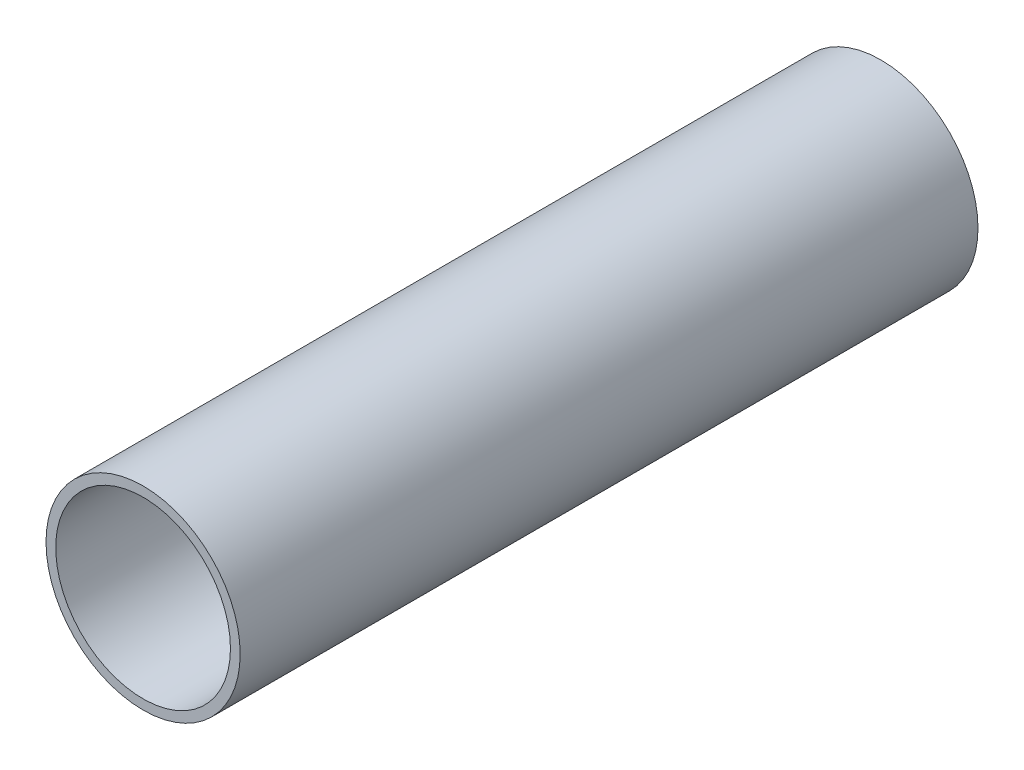
SolidWorks part; units mm, degrees
ref_plane "Front Plane" through (0, 0, 0) normal (0, 0, 1) x (1, 0, 0)
ref_plane "Top Plane" through (0, 0, 0) normal (0, 1, 0) x (1, 0, 0)
ref_plane "Right Plane" through (0, 0, 0) normal (1, 0, 0) x (0, 0, -1)
sketch "Sketch1" plane through (0, 0, 0) normal (0, 0, 1) x (1, 0, 0)
  circle A0 centre (35, 0) radius 2.5
  dimension "D1" = 5
extrude "Boss-Extrude1" add sketch "Sketch1" along normal blind 19
sketch "Sketch3" plane through (0, 0, 19) normal (0, 0, 1) x (1, 0, 0)
  circle A0 centre (35, 0) radius 1.6
  circle A1 centre (35, 0) radius 2.25
  dimension "D1" = 3.2
  dimension "D2" = 4.5
extrude "Cut-Extrude1" cut sketch "Sketch3" against normal up to next contours A0
extrude "Cut-Extrude2" cut sketch "Sketch3<3>" against normal blind 6
sketch "Sketch3<3>" plane through (0, 0, 19) normal (0, 0, 1) x (1, 0, 0) same geometry as "Sketch3"
ref_plane "Plane1" through (0, 0, 9.5) normal (0, 0, 1) x (1, 0, 0)
mirror "Mirror1" about plane through (0, 0, 9.5) normal (0, 0, 1) of "Cut-Extrude2"
equation "\"RingPostIn\"=5"
equation "\"D1@Sketch1\"=\"RingPostIn\""
equation "\"RingPinShaft\"= 5"
equation "\"CenterBearingOut\"=32"
equation "\"m3Thru\"=3.2"
equation "\"D1@Sketch3\"=\"m3Thru\""
equation "\"m3Insert\"=4.5"
equation "\"D2@Sketch3\"=\"m3Insert\""
